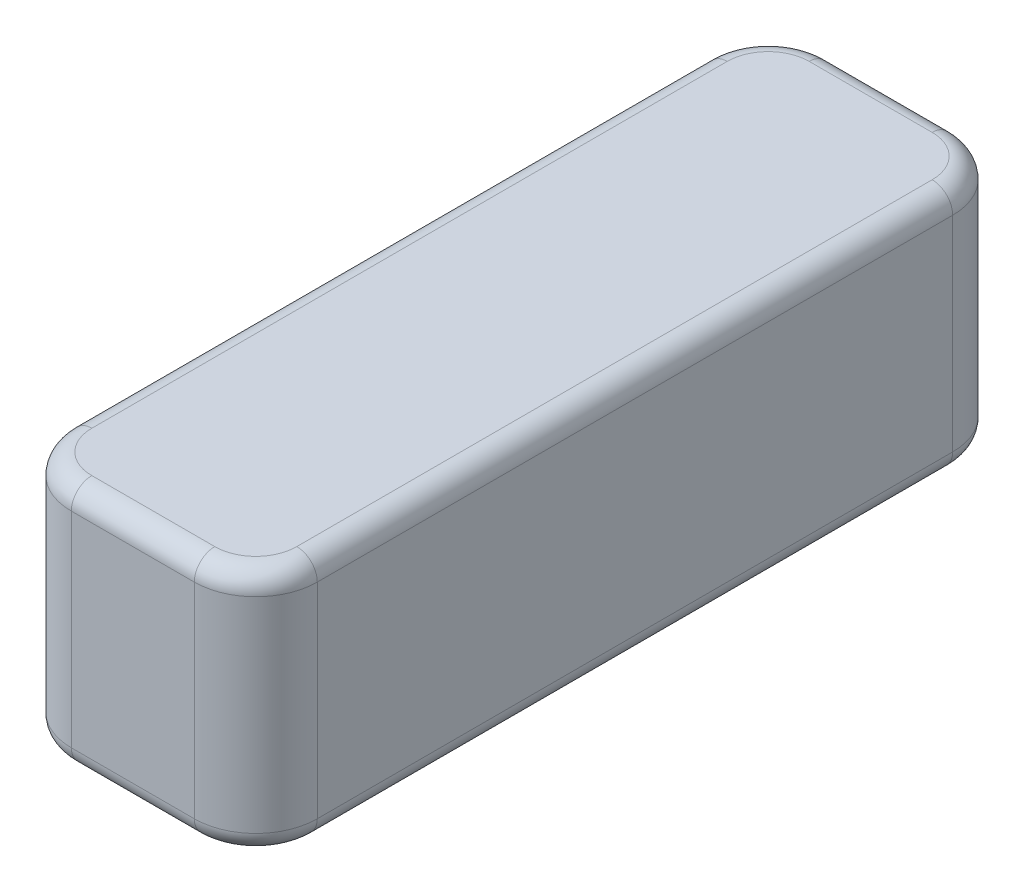
SolidWorks part; units mm, degrees
ref_plane "Front Plane" through (0, 0, 0) normal (0, 0, 1) x (1, 0, 0)
ref_plane "Top Plane" through (0, 0, 0) normal (0, 1, 0) x (1, 0, 0)
ref_plane "Right Plane" through (0, 0, 0) normal (1, 0, 0) x (0, 0, -1)
sketch "Sketch1" plane through (0, 0, 0) normal (0, 1, 0) x (1, 0, 0)
  line L1 (-15.24, -46.99) -> (15.24, -46.99)
  line L2 (-15.24, -46.99) -> (-15.24, 46.99)
  line L3 (-15.24, 46.99) -> (15.24, 46.99)
  line L4 (15.24, -46.99) -> (15.24, 46.99)
  line L5 (-15.24, -46.99) -> (15.24, 46.99) construction
  line L6 (-15.24, 46.99) -> (15.24, -46.99) construction
  point P0 (0, 0)
  dimension "D1" = 93.98
  dimension "D2" = 30.48
extrude "Boss-Extrude1" add sketch "Sketch1" along normal blind 30.48
fillet "Fillet2" radius 2.54 8 edges at (0, 0, -46.99) (-15.24, 0, 0) (0, 0, 46.99) (15.24, 0, 0) (0, 30.48, 46.99) (-15.24, 30.48, 0) (0, 30.48, -46.99) (15.24, 30.48, 0)
fillet "Fillet3" radius 7.62 12 edges at (-14.4961, 0.7439, 46.2461) (-14.4961, 29.7361, 46.2461) (14.4961, 0.7439, 46.2461) (14.4961, 29.7361, 46.2461) (14.4961, 0.7439, -46.2461) (14.4961, 29.7361, -46.2461) (-14.4961, 0.7439, -46.2461) (-14.4961, 29.7361, -46.2461) (-15.24, 15.24, -46.99) (15.24, 15.24, -46.99) (15.24, 15.24, 46.99) (-15.24, 15.24, 46.99)
